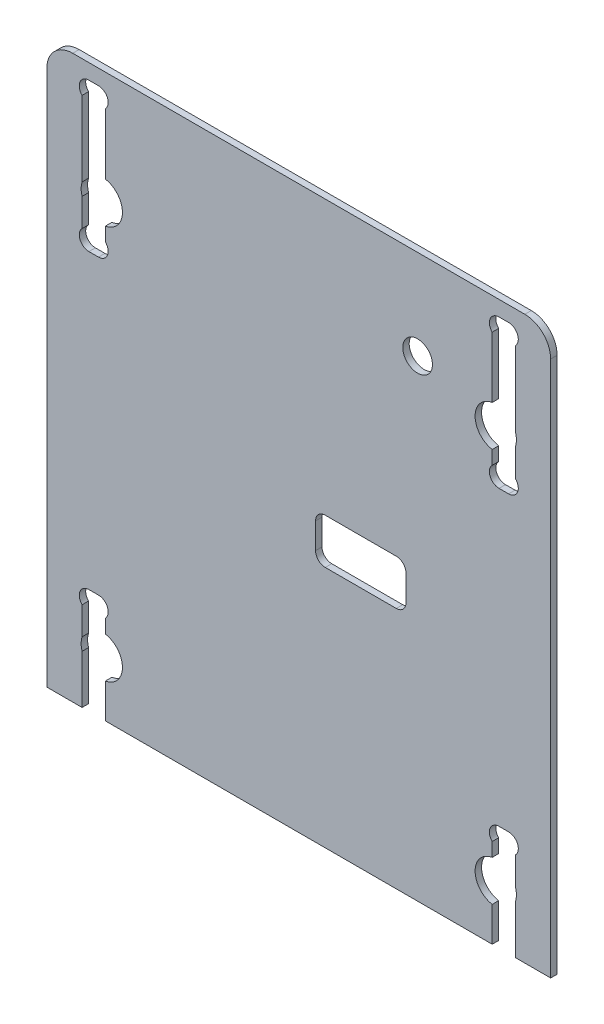
SolidWorks part; units mm, degrees
ref_plane "Front Plane" through (0, 0, 0) normal (0, 0, 1) x (1, 0, 0)
ref_plane "Top Plane" through (0, 0, 0) normal (0, 1, 0) x (1, 0, 0)
ref_plane "Right Plane" through (0, 0, 0) normal (1, 0, 0) x (0, 0, -1)
sketch "Sketch1" plane through (0, 0, 0) normal (0, 0, 1) x (1, 0, 0)
  line L1 (19.5, -7.325) -> (19.5, 4.675)
  line L2 (19.5, 24) -> (-19.5, 24)
  line L7 (14.975, 13.6738) -> (14.975, 12.6107)
  line L8 (14.975, 21.5393) -> (14.975, 16.8262)
  line L9 (16.2447, 22.8197) -> (15.5053, 22.8197)
  line L10 (16.775, 15.7341) -> (16.775, 21.5393)
  line L11 (16.775, 12.6107) -> (16.775, 14.7659)
  line L12 (15.5053, 11.3303) -> (16.2447, 11.3303)
  line L13 (14.975, 13.6738) -> (14.975, 12.6107)
  line L14 (14.975, 21.5393) -> (14.975, 16.8262)
  line L15 (16.2447, 22.8197) -> (15.5053, 22.8197)
  line L16 (16.775, 15.7341) -> (16.775, 21.5393)
  line L17 (16.775, 12.6107) -> (16.775, 14.7659)
  line L18 (15.5053, 11.3303) -> (16.2447, 11.3303)
  line L19 (-16.775, 14.7659) -> (-16.775, 12.6107)
  line L20 (-16.775, 21.5393) -> (-16.775, 15.7341)
  line L21 (-15.5053, 22.8197) -> (-16.2447, 22.8197)
  line L22 (-14.975, 16.8262) -> (-14.975, 21.5393)
  line L23 (-14.975, 12.6107) -> (-14.975, 13.6738)
  line L24 (-16.2447, 11.3303) -> (-15.5053, 11.3303)
  line L25 (-16.775, 14.7659) -> (-16.775, 12.6107)
  line L26 (-16.775, 21.5393) -> (-16.775, 15.7341)
  line L27 (-15.5053, 22.8197) -> (-16.2447, 22.8197)
  line L28 (-14.975, 16.8262) -> (-14.975, 21.5393)
  line L29 (-14.975, 12.6107) -> (-14.975, 13.6738)
  line L30 (-16.2447, 11.3303) -> (-15.5053, 11.3303)
  line L33 (-19.5, -19.5) -> (-16.775, -19.5)
  line L34 (-16.775, -19.5) -> (-16.775, -15.7341)
  line L35 (-16.775, -14.7659) -> (-16.775, -12.6107)
  line L36 (-16.2447, -11.3303) -> (-15.5053, -11.3303)
  line L37 (-14.975, -12.6107) -> (-14.975, -13.6738)
  line L38 (-14.975, -16.8262) -> (-14.975, -19.5)
  line L39 (-14.975, -19.5) -> (14.975, -19.5)
  line L40 (14.975, -19.5) -> (14.975, -16.8262)
  line L41 (14.975, -13.6738) -> (14.975, -12.6107)
  line L42 (15.5053, -11.3303) -> (16.2447, -11.3303)
  line L43 (16.775, -12.6107) -> (16.775, -14.7659)
  line L44 (16.775, -15.7341) -> (16.775, -19.5)
  line L45 (16.775, -19.5) -> (19.5, -19.5)
  line L46 (19.5, -19.5) -> (19.5, -7.325)
  line L47 (19.5, -7.325) -> (17.5, -7.325)
  line L48 (17.5, -7.325) -> (17.5, -9.4)
  line L49 (16.75, -10.15) -> (13.05, -10.15)
  line L50 (12.3, -10.9) -> (12.3, -16.7496)
  line L51 (11.55, -17.4996) -> (-11.55, -17.4996)
  line L52 (-12.3, -16.7496) -> (-12.3, -10.9)
  line L53 (-13.05, -10.15) -> (-16.75, -10.15)
  line L54 (-17.5, -9.4) -> (-17.5, 9.4)
  line L55 (-16.75, 10.15) -> (-13.05, 10.15)
  line L56 (-12.3, 10.9) -> (-12.3, 16.7496)
  line L57 (-11.55, 17.4996) -> (6.3156, 17.4996)
  line L58 (9.2, 14.9) -> (11.55, 14.9)
  line L59 (12.3, 14.15) -> (12.3, 10.9)
  line L60 (13.05, 10.15) -> (16.75, 10.15)
  line L61 (17.5, 9.4) -> (17.5, 4.675)
  line L62 (17.5, 4.675) -> (19.5, 4.675)
  line L63 (19.5, 4.675) -> (19.5, 35.2)
  line L64 (15.5, 39.2) -> (-15.5, 39.2)
  line L65 (-19.5, 35.2) -> (-19.5, -19.5)
  line L66 (-19.5, -19.5) -> (-16.775, -19.5)
  line L67 (-16.775, -19.5) -> (-16.775, -15.7341)
  line L68 (-16.775, -14.7659) -> (-16.775, -12.6107)
  line L69 (-16.2447, -11.3303) -> (-15.5053, -11.3303)
  line L70 (-14.975, -12.6107) -> (-14.975, -13.6738)
  line L71 (-14.975, -16.8262) -> (-14.975, -19.5)
  line L72 (-14.975, -19.5) -> (14.975, -19.5)
  line L73 (14.975, -19.5) -> (14.975, -16.8262)
  line L74 (14.975, -13.6738) -> (14.975, -12.6107)
  line L75 (15.5053, -11.3303) -> (16.2447, -11.3303)
  line L76 (16.775, -12.6107) -> (16.775, -14.7659)
  line L77 (16.775, -15.7341) -> (16.775, -19.5)
  line L78 (16.775, -19.5) -> (19.5, -19.5)
  line L79 (19.5, -19.5) -> (19.5, -7.325)
  line L80 (19.5, -7.325) -> (17.5, -7.325)
  line L81 (17.5, -7.325) -> (17.5, -9.4)
  line L82 (16.75, -10.15) -> (13.05, -10.15)
  line L83 (12.3, -10.9) -> (12.3, -16.7496)
  line L84 (11.55, -17.4996) -> (-11.55, -17.4996)
  line L85 (-12.3, -16.7496) -> (-12.3, -10.9)
  line L86 (-13.05, -10.15) -> (-16.75, -10.15)
  line L87 (-17.5, -9.4) -> (-17.5, 9.4)
  line L88 (-16.75, 10.15) -> (-13.05, 10.15)
  line L89 (-12.3, 10.9) -> (-12.3, 16.7496)
  line L90 (-11.55, 17.4996) -> (6.3156, 17.4996)
  line L91 (9.2, 14.9) -> (11.55, 14.9)
  line L92 (12.3, 14.15) -> (12.3, 10.9)
  line L93 (13.05, 10.15) -> (16.75, 10.15)
  line L94 (17.5, 9.4) -> (17.5, 4.675)
  line L95 (17.5, 4.675) -> (19.5, 4.675)
  line L96 (19.5, 4.675) -> (19.5, 35.2)
  line L97 (15.5, 39.2) -> (-15.5, 39.2)
  line L98 (-19.5, 35.2) -> (-19.5, -19.5)
  circle A5 centre (9.2, 17.05) radius 1.15 construction
  circle A6 centre (9.2, 17.05) radius 1.15
  arc A17 (14.975, 12.6107) -> (15.5053, 11.3303) centre (15.5053, 12.0803) ccw
  arc A18 (14.975, 16.8262) -> (14.975, 13.6738) centre (15.25, 15.25) ccw
  arc A19 (15.5053, 22.8197) -> (14.975, 21.5393) centre (15.5053, 22.0697) ccw
  arc A20 (16.775, 21.5393) -> (16.2447, 22.8197) centre (16.2447, 22.0697) ccw
  arc A21 (16.775, 14.7659) -> (16.775, 15.7341) centre (15.25, 15.25) ccw
  arc A22 (16.2447, 11.3303) -> (16.775, 12.6107) centre (16.2447, 12.0803) ccw
  arc A23 (14.975, 12.6107) -> (15.5053, 11.3303) centre (15.5053, 12.0803) ccw
  arc A24 (14.975, 16.8262) -> (14.975, 13.6738) centre (15.25, 15.25) ccw
  arc A25 (15.5053, 22.8197) -> (14.975, 21.5393) centre (15.5053, 22.0697) ccw
  arc A26 (16.775, 21.5393) -> (16.2447, 22.8197) centre (16.2447, 22.0697) ccw
  arc A27 (16.775, 14.7659) -> (16.775, 15.7341) centre (15.25, 15.25) ccw
  arc A28 (16.2447, 11.3303) -> (16.775, 12.6107) centre (16.2447, 12.0803) ccw
  arc A29 (-16.775, 12.6107) -> (-16.2447, 11.3303) centre (-16.2447, 12.0803) ccw
  arc A30 (-16.775, 15.7341) -> (-16.775, 14.7659) centre (-15.25, 15.25) ccw
  arc A31 (-16.2447, 22.8197) -> (-16.775, 21.5393) centre (-16.2447, 22.0697) ccw
  arc A32 (-14.975, 21.5393) -> (-15.5053, 22.8197) centre (-15.5053, 22.0697) ccw
  arc A33 (-16.775, -14.7659) -> (-16.775, -15.7341) centre (-15.25, -15.25) ccw
  arc A34 (-16.2447, -11.3303) -> (-16.775, -12.6107) centre (-16.2447, -12.0803) ccw
  arc A35 (-14.975, -12.6107) -> (-15.5053, -11.3303) centre (-15.5053, -12.0803) ccw
  arc A36 (-14.975, -16.8262) -> (-14.975, -13.6738) centre (-15.25, -15.25) ccw
  arc A37 (14.975, -13.6738) -> (14.975, -16.8262) centre (15.25, -15.25) ccw
  arc A38 (15.5053, -11.3303) -> (14.975, -12.6107) centre (15.5053, -12.0803) ccw
  arc A39 (16.775, -12.6107) -> (16.2447, -11.3303) centre (16.2447, -12.0803) ccw
  arc A40 (16.775, -15.7341) -> (16.775, -14.7659) centre (15.25, -15.25) ccw
  arc A41 (16.75, -10.15) -> (17.5, -9.4) centre (16.75, -9.4) ccw
  arc A42 (13.05, -10.15) -> (12.3, -10.9) centre (13.05, -10.9) ccw
  arc A43 (11.55, -17.4996) -> (12.3, -16.7496) centre (11.55, -16.7496) ccw
  arc A44 (-12.3, -16.7496) -> (-11.55, -17.4996) centre (-11.55, -16.7496) ccw
  arc A45 (-12.3, -10.9) -> (-13.05, -10.15) centre (-13.05, -10.9) ccw
  arc A46 (-17.5, -9.4) -> (-16.75, -10.15) centre (-16.75, -9.4) ccw
  arc A47 (-16.75, 10.15) -> (-17.5, 9.4) centre (-16.75, 9.4) ccw
  arc A48 (-13.05, 10.15) -> (-12.3, 10.9) centre (-13.05, 10.9) ccw
  arc A49 (-11.55, 17.4996) -> (-12.3, 16.7496) centre (-11.55, 16.7496) ccw
  arc A50 (7.0616, 16.8273) -> (6.3156, 17.4996) centre (6.3156, 16.7496) ccw
  arc A51 (7.0616, 16.8273) -> (9.2, 14.9) centre (9.2, 17.05) ccw
  arc A52 (12.3, 14.15) -> (11.55, 14.9) centre (11.55, 14.15) ccw
  arc A53 (12.3, 10.9) -> (13.05, 10.15) centre (13.05, 10.9) ccw
  arc A54 (17.5, 9.4) -> (16.75, 10.15) centre (16.75, 9.4) ccw
  arc A55 (19.5, 35.2) -> (15.5, 39.2) centre (15.5, 35.2) ccw
  arc A56 (-15.5, 39.2) -> (-19.5, 35.2) centre (-15.5, 35.2) ccw
  arc A57 (-16.775, -14.7659) -> (-16.775, -15.7341) centre (-15.25, -15.25) ccw
  arc A58 (-16.2447, -11.3303) -> (-16.775, -12.6107) centre (-16.2447, -12.0803) ccw
  arc A59 (-14.975, -12.6107) -> (-15.5053, -11.3303) centre (-15.5053, -12.0803) ccw
  arc A60 (-14.975, -16.8262) -> (-14.975, -13.6738) centre (-15.25, -15.25) ccw
  arc A61 (14.975, -13.6738) -> (14.975, -16.8262) centre (15.25, -15.25) ccw
  arc A62 (15.5053, -11.3303) -> (14.975, -12.6107) centre (15.5053, -12.0803) ccw
  arc A63 (16.775, -12.6107) -> (16.2447, -11.3303) centre (16.2447, -12.0803) ccw
  arc A64 (16.775, -15.7341) -> (16.775, -14.7659) centre (15.25, -15.25) ccw
  arc A65 (16.75, -10.15) -> (17.5, -9.4) centre (16.75, -9.4) ccw
  arc A66 (13.05, -10.15) -> (12.3, -10.9) centre (13.05, -10.9) ccw
  arc A67 (11.55, -17.4996) -> (12.3, -16.7496) centre (11.55, -16.7496) ccw
  arc A68 (-12.3, -16.7496) -> (-11.55, -17.4996) centre (-11.55, -16.7496) ccw
  arc A69 (-12.3, -10.9) -> (-13.05, -10.15) centre (-13.05, -10.9) ccw
  arc A70 (-17.5, -9.4) -> (-16.75, -10.15) centre (-16.75, -9.4) ccw
  arc A71 (-16.75, 10.15) -> (-17.5, 9.4) centre (-16.75, 9.4) ccw
  arc A72 (-13.05, 10.15) -> (-12.3, 10.9) centre (-13.05, 10.9) ccw
  arc A73 (-11.55, 17.4996) -> (-12.3, 16.7496) centre (-11.55, 16.7496) ccw
  arc A74 (7.0616, 16.8273) -> (6.3156, 17.4996) centre (6.3156, 16.7496) ccw
  arc A75 (7.0616, 16.8273) -> (9.2, 14.9) centre (9.2, 17.05) ccw
  arc A76 (12.3, 14.15) -> (11.55, 14.9) centre (11.55, 14.15) ccw
  arc A77 (12.3, 10.9) -> (13.05, 10.15) centre (13.05, 10.9) ccw
  arc A78 (17.5, 9.4) -> (16.75, 10.15) centre (16.75, 9.4) ccw
  arc A79 (19.5, 35.2) -> (15.5, 39.2) centre (15.5, 35.2) ccw
  arc A80 (-15.5, 39.2) -> (-19.5, 35.2) centre (-15.5, 35.2) ccw
  arc A81 (-14.975, 13.6738) -> (-14.975, 16.8262) centre (-15.25, 15.25) ccw
  arc A82 (-15.5053, 11.3303) -> (-14.975, 12.6107) centre (-15.5053, 12.0803) ccw
  arc A83 (-16.775, 12.6107) -> (-16.2447, 11.3303) centre (-16.2447, 12.0803) ccw
  arc A84 (-16.775, 15.7341) -> (-16.775, 14.7659) centre (-15.25, 15.25) ccw
  arc A85 (-16.2447, 22.8197) -> (-16.775, 21.5393) centre (-16.2447, 22.0697) ccw
  arc A86 (-14.975, 21.5393) -> (-15.5053, 22.8197) centre (-15.5053, 22.0697) ccw
  arc A87 (-14.975, 13.6738) -> (-14.975, 16.8262) centre (-15.25, 15.25) ccw
  arc A88 (-15.5053, 11.3303) -> (-14.975, 12.6107) centre (-15.5053, 12.0803) ccw
  dimension "D2" = 0
  dimension "D4" = 43.5
  dimension "D1" = 0
  dimension "D3" = 0
extrude "Shape" add sketch "Sketch1" along normal blind 0.5 contours A88 L30 A83 L25 A84 L26 A85 L2 L98 L66 L67 A57 L68 A58 L69 A59 L70 A60 L71 L72 L73 A61 L74 A62 L75 A63 L76 A64 L77 L78 L79 L80 L81 A65 L82 A66 L83 A67 L84 A68 L85 A69 L86 A70 L87 A71 L88 A72 L89 A73 L90 | L94 A78 L93 A77 L92 A76 L91 A75 A74 L90 A73 L89 A72 L88 A71 L87 A70 L86 A69 L85 A68 L84 A67 L83 A66 L82 A65 L81 L80 L1 L95 region at (0.2943, -0.2209, 0) region at (18.9158, -13.4125, 0)
sketch "Sketch2" plane through (0, 0, 0.5) normal (0, 0, 1) x (1, 0, 0)
  line L0 (9.3, 6.3018) -> (0.3, 6.3018) construction
  line L1 (9.3, 6.3018) -> (0.3, 6.3018)
  line L2 (4.8, 6.3018) -> (4.8, -19.5) construction
  line L3 (-14.975, -19.5) -> (14.975, -19.5) construction
  line L5 (2.05, -0.6982) -> (7.55, -0.6982)
  line L6 (1.3, 0.0518) -> (1.3, 2.0518)
  line L7 (2.05, 2.8018) -> (7.55, 2.8018)
  line L8 (8.3, 0.0518) -> (8.3, 2.0518)
  line L9 (1.3, -0.6982) -> (8.3, 2.8018) construction
  line L10 (1.3, 2.8018) -> (8.3, -0.6982) construction
  arc A0 (7.55, 2.8018) -> (8.3, 2.0518) centre (7.55, 2.0518) cw
  arc A1 (7.55, -0.6982) -> (8.3, 0.0518) centre (7.55, 0.0518) ccw
  arc A2 (2.05, -0.6982) -> (1.3, 0.0518) centre (2.05, 0.0518) cw
  arc A3 (1.3, 2.0518) -> (2.05, 2.8018) centre (2.05, 2.0518) cw
  point P6 (4.8, 1.0518)
  dimension "D4" = 0.75
  dimension "D1" = 7
  dimension "D2" = 3.5
  dimension "D3" = 3.5
extrude "Camera connector hole" cut sketch "Sketch2" against normal up to next contours L5 L8 L7 L6 region at (4.8, 1.0518, 0.5)
fillet "Fillet1" radius 2 2 edges at (19.5, 24, 0.25) (-19.5, 24, 0.25)
